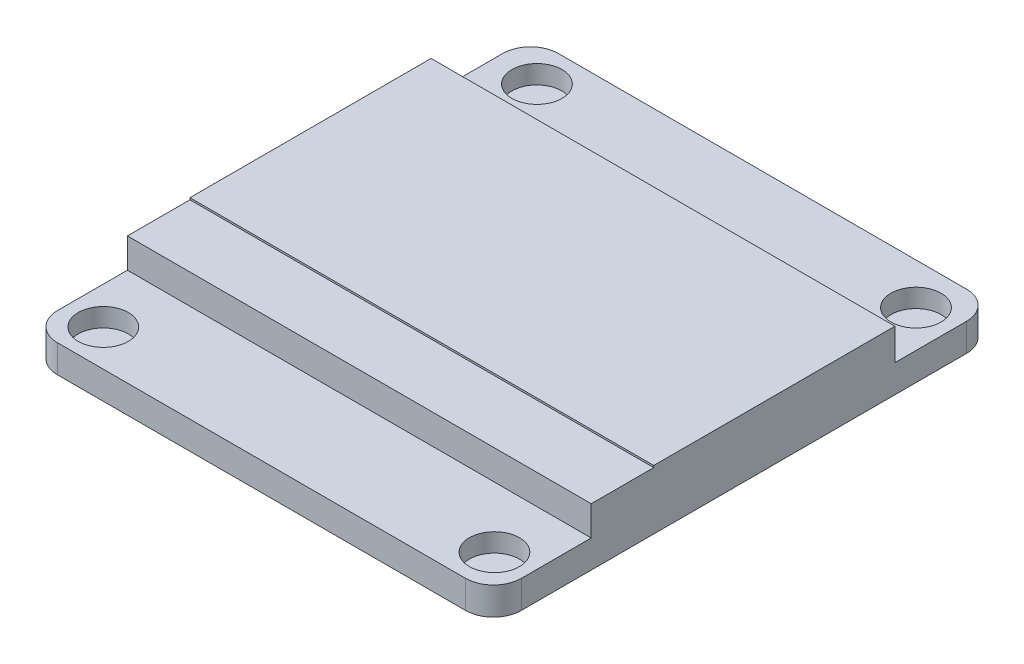
SolidWorks part; units mm, degrees
ref_plane "前视基准面" through (0, 0, 0) normal (0, 0, 1) x (1, 0, 0)
ref_plane "上视基准面" through (0, 0, 0) normal (0, 1, 0) x (1, 0, 0)
ref_plane "右视基准面" through (0, 0, 0) normal (1, 0, 0) x (0, 0, -1)
sketch "草图2" plane through (0, 0, 0) normal (0, 1, 0) x (1, 0, 0)
  line L1 (-118.2575, 92.3321) -> (-96.2575, 92.3321)
  line L2 (-119.7575, 90.8321) -> (-119.7575, 66.8321)
  line L3 (-118.2575, 65.3321) -> (-96.2575, 65.3321)
  line L4 (-94.7575, 90.8321) -> (-94.7575, 66.8321)
  arc A0 (-96.2575, 92.3321) -> (-94.7575, 90.8321) centre (-96.2575, 90.8321) cw
  arc A1 (-96.2575, 65.3321) -> (-94.7575, 66.8321) centre (-96.2575, 66.8321) ccw
  arc A2 (-119.7575, 66.8321) -> (-118.2575, 65.3321) centre (-118.2575, 66.8321) ccw
  arc A3 (-118.2575, 92.3321) -> (-119.7575, 90.8321) centre (-118.2575, 90.8321) ccw
  point P6 (-94.7575, 92.3321)
  point P9 (-94.7575, 65.3321)
  point P14 (-119.7575, 92.3321)
  dimension "D3" = 1.5
  dimension "D4" = 1.5
  dimension "D1" = 25
  dimension "D2" = 27
extrude "凸台-拉伸1" add sketch "草图2" along normal blind 1.5
sketch "草图3" plane through (0, 1.5, 0) normal (0, 1, 0) x (1, 0, 0)
  line L0 (-96.2575, 92.3321) -> (-118.2575, 92.3321) construction
  line L1 (-94.7575, 66.8321) -> (-94.7575, 90.8321) construction
  line L2 (-118.2575, 65.3321) -> (-96.2575, 65.3321) construction
  line L3 (-119.7575, 90.8321) -> (-119.7575, 66.8321) construction
  circle A0 centre (-117.413, 90.3321) radius 1.35
  circle A1 centre (-96.7575, 90.108) radius 1.35
  circle A2 centre (-96.7044, 67.3321) radius 1.35
  circle A3 centre (-117.7575, 67.3032) radius 1.35
  dimension "D5" = 2.7
  dimension "D1" = 2
  dimension "D2" = 2
  dimension "D3" = 2
  dimension "D4" = 2
extrude "切除-拉伸1" cut sketch "草图3" against normal blind 1
sketch "草图4" plane through (0, 1.5, 0) normal (0, 1, 0) x (1, 0, 0)
  line L0 (-119.7575, 90.8321) -> (-119.7575, 66.8321) construction
  line L1 (-119.7575, 86.9721) -> (-94.7575, 86.9721)
  line L2 (-119.7575, 86.9721) -> (-119.7575, 70.6021)
  line L3 (-119.7575, 70.6021) -> (-94.7575, 70.6021)
  line L4 (-94.7575, 86.9721) -> (-94.7575, 70.6021)
  line L5 (-94.7575, 66.8321) -> (-94.7575, 90.8321) construction
  line L6 (-96.2575, 92.3321) -> (-118.2575, 92.3321) construction
  dimension "D1" = 5.36
  dimension "D2" = 16.37
extrude "凸台-拉伸2" add sketch "草图4" along normal blind 1.6
sketch "草图5" plane through (0, 3.1, 0) normal (0, 1, 0) x (1, 0, 0)
  line L0 (-94.7575, 70.6021) -> (-94.7575, 86.9721) construction
  line L1 (-119.7575, 86.9721) -> (-94.7575, 86.9721)
  line L2 (-119.7575, 86.9721) -> (-119.7575, 73.9721)
  line L3 (-119.7575, 73.9721) -> (-94.7575, 73.9721)
  line L4 (-94.7575, 86.9721) -> (-94.7575, 73.9721)
  dimension "D1" = 13
extrude "凸台-拉伸3" add sketch "草图5" along normal blind 0.1
